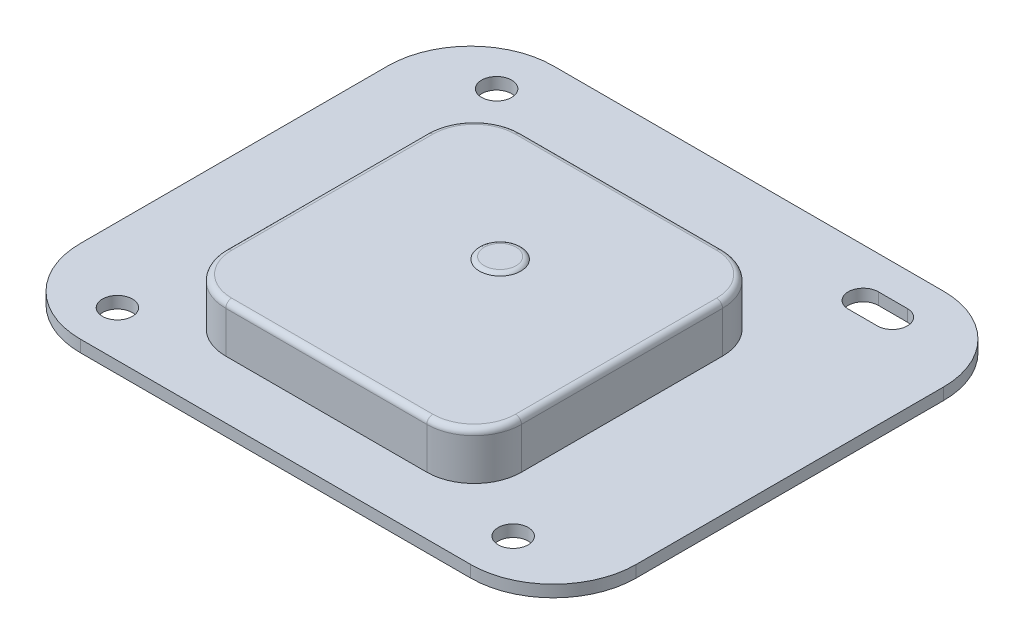
SolidWorks part; units mm, degrees
ref_plane "Front Plane" through (0, 0, 0) normal (0, 0, 1) x (1, 0, 0)
ref_plane "Top Plane" through (0, 0, 0) normal (0, 1, 0) x (1, 0, 0)
ref_plane "Right Plane" through (0, 0, 0) normal (1, 0, 0) x (0, 0, -1)
sketch "Sketch3" plane through (0, 0, 0) normal (0, 1, 0) x (1, 0, 0)
  line L0 (23.5, 20) -> (23.5, -20) construction
  line L1 (-23.5, -20) -> (23.5, -20) construction
  line L2 (-23.5, 20) -> (-23.5, -20) construction
  line L3 (-23.5, 20) -> (23.5, 20) construction
  line L4 (23.5, 20) -> (23.5, -20)
  line L5 (-23.5, -20) -> (23.5, -20)
  line L6 (-23.5, 20) -> (-23.5, -20)
  line L7 (-23.5, 20) -> (23.5, 20)
  line L8 (5.2, -11.1) -> (16.8, -11.1) construction
  line L9 (16.8, 3.9) -> (16.8, -11.1) construction
  line L10 (5.2, 3.9) -> (16.8, 3.9) construction
  line L11 (5.2, 3.9) -> (5.2, -11.1) construction
  line L12 (-20.5, 10) -> (-14.9, 10) construction
  line L13 (-20.5, 10) -> (-20.5, -0.9) construction
  line L14 (-20.5, -0.9) -> (-14.9, -0.9) construction
  line L15 (-14.9, 10) -> (-14.9, -0.9) construction
  line L16 (5.2, -11.1) -> (16.8, -11.1)
  line L17 (16.8, 3.9) -> (16.8, -11.1)
  line L18 (5.2, 3.9) -> (16.8, 3.9)
  line L19 (5.2, 3.9) -> (5.2, -11.1)
  line L20 (-20.5, 10) -> (-14.9, 10)
  line L21 (-20.5, 10) -> (-20.5, -0.9)
  line L22 (-20.5, -0.9) -> (-14.9, -0.9)
  line L23 (-14.9, 10) -> (-14.9, -0.9)
  circle A0 centre (-17.23, 15.93) radius 1.27 construction
  circle A1 centre (16.23, 15.93) radius 1.27 construction
  circle A2 centre (-17.23, -16.13) radius 1.27 construction
  circle A3 centre (16.23, -16.13) radius 1.27 construction
  circle A4 centre (-17.23, 15.93) radius 1.27
  circle A5 centre (16.23, 15.93) radius 1.27
  circle A6 centre (-17.23, -16.13) radius 1.27
  circle A7 centre (16.23, -16.13) radius 1.27
sketch "Sketch4" plane through (0, 0, 0) normal (0, 1, 0) x (1, 0, 0)
  line L0 (13.77, 14.66) -> (16.23, 14.66)
  line L1 (13.77, 17.2) -> (16.23, 17.2)
  line L4 (23.5, -20) -> (23.5, 20)
  line L5 (-23.5, -20) -> (23.5, -20)
  line L6 (-23.5, 20) -> (-23.5, -20)
  line L7 (23.5, 20) -> (-23.5, 20)
  line L8 (23.5, -20) -> (23.5, 20)
  line L9 (-23.5, -20) -> (23.5, -20)
  line L10 (-23.5, 20) -> (-23.5, -20)
  line L11 (23.5, 20) -> (-23.5, 20)
  arc A0 (13.77, 17.2) -> (13.77, 14.66) centre (13.77, 15.93) ccw
  circle A1 centre (16.23, -16.13) radius 1.27
  circle A2 centre (16.23, -16.13) radius 1.27
  circle A3 centre (-17.23, -16.13) radius 1.27
  circle A4 centre (-17.23, -16.13) radius 1.27
  circle A5 centre (16.23, 15.93) radius 1.27
  arc A6 (16.23, 14.66) -> (16.23, 17.2) centre (16.23, 15.93) ccw
  circle A7 centre (-17.23, 15.93) radius 1.27
  circle A8 centre (-17.23, 15.93) radius 1.27
  point P18 (12.5, 15.93)
  point P19 (17.5, 15.93)
  dimension "D6" = 5
  dimension "D1" = 0
  dimension "D2" = 0
  dimension "D3" = 0
  dimension "D4" = 0
  dimension "D5" = 0
extrude "Boss-Extrude1" add sketch "Sketch4" along normal blind 1
fillet "Fillet1" radius 7 4 edges at (-23.5, 0.5, -20) (23.5, 0.5, -20) (-23.5, 0.5, 20) (23.5, 0.5, 20)
sketch "Sketch5" plane through (0, 0, 0) normal (0, -1, 0) x (1, 0, 0)
  line L0 (5.2, -3.9) -> (5.2, 11.1) construction
  line L1 (5.2, 11.1) -> (16.8, 11.1) construction
  line L2 (5.2, -3.9) -> (16.8, -3.9) construction
  line L3 (16.8, -3.9) -> (16.8, 11.1) construction
  line L4 (5.2, -3.9) -> (5.2, 11.1)
  line L5 (5.2, 11.1) -> (16.8, 11.1)
  line L6 (5.2, -3.9) -> (16.8, -3.9)
  line L7 (16.8, -3.9) -> (16.8, 11.1)
extrude "Boss-Extrude2" add sketch "Sketch5" along normal blind 2.5
sketch "Sketch6" plane through (0, 0, 0) normal (0, -1, 0) x (1, 0, 0)
  line L0 (-20.5, -10) -> (-20.5, 0.9) construction
  line L1 (-20.5, 0.9) -> (-14.9, 0.9) construction
  line L2 (-20.5, -10) -> (-14.9, -10) construction
  line L3 (-14.9, -10) -> (-14.9, 0.9) construction
  line L4 (-20.5, -10) -> (-20.5, 0.9)
  line L5 (-20.5, 0.9) -> (-14.9, 0.9)
  line L6 (-20.5, -10) -> (-14.9, -10)
  line L7 (-14.9, -10) -> (-14.9, 0.9)
extrude "Boss-Extrude3" add sketch "Sketch6" along normal blind 4.5
sketch "Sketch7" plane through (0, 1, 0) normal (0, 1, 0) x (1, 0, 0)
  line L0 (23.5, -13) -> (23.5, 13) construction
  line L1 (-13.1, 9.9) -> (11.9, 9.9)
  line L2 (-13.1, 9.9) -> (-13.1, -15.1)
  line L3 (-13.1, -15.1) -> (11.9, -15.1)
  line L4 (11.9, 9.9) -> (11.9, -15.1)
  line L5 (16.5, 20) -> (-16.5, 20) construction
  dimension "D1" = 25
  dimension "D2" = 11.6
  dimension "D3" = 10.1
extrude "Boss-Extrude4" add sketch "Sketch7" along normal blind 4
fillet "Fillet2" radius 4 4 edges at (-13.1, 3, -9.9) (-13.1, 3, 15.1) (11.9, 3, 15.1) (11.9, 3, -9.9)
sketch "Sketch8" plane through (0, 5, 0) normal (0, 1, 0) x (1, 0, 0)
  line L0 (-0.6, 9.9) -> (-0.6, -15.1) construction
  line L4 (11.9, 9.9) -> (-13.1, 9.9)
  line L5 (11.9, -15.1) -> (11.9, 9.9)
  line L6 (-13.1, -15.1) -> (11.9, -15.1)
  line L7 (-13.1, 9.9) -> (-13.1, -15.1)
  line L8 (11.9, 9.9) -> (-13.1, 9.9) construction
  line L9 (11.9, -15.1) -> (11.9, 9.9) construction
  line L10 (-13.1, -15.1) -> (11.9, -15.1) construction
  line L11 (-13.1, 9.9) -> (-13.1, -15.1) construction
  circle A0 centre (-0.6, -0.4) radius 1.75
  dimension "D2" = 3.5
  dimension "D3" = 10.3
  dimension "D1" = 0
extrude "Boss-Extrude5" add sketch "Sketch8" along normal blind 0.2
fillet "Fillet3" radius 0.5 1 edges at (-0.6, 5.2, 2.15)
sketch "Sketch9" plane through (0, 0, 0) normal (0, -1, 0) x (1, 0, 0)
  line L0 (16.5, -20) -> (-16.5, -20) construction
  line L1 (-5, -15.2) -> (3, -15.2)
  line L2 (-5, -15.2) -> (-5, -20.7)
  line L3 (-5, -20.7) -> (3, -20.7)
  line L4 (3, -15.2) -> (3, -20.7)
  line L5 (-23.5, -13) -> (-23.5, 13) construction
  dimension "D1" = 0.7
  dimension "D2" = 8
  dimension "D3" = 5.5
  dimension "D4" = 18.5
extrude "Boss-Extrude6" add sketch "Sketch9" along normal blind 2.4
fillet "Fillet4" radius 0.5 8 edges at (10.7284, 5, 13.9284) (-0.6, 5, 15.1) (-11.9284, 5, 13.9284) (-13.1, 5, 2.6) (-11.9284, 5, -8.7284) (-0.6, 5, -9.9) (10.7284, 5, -8.7284) (11.9, 5, 2.6)
